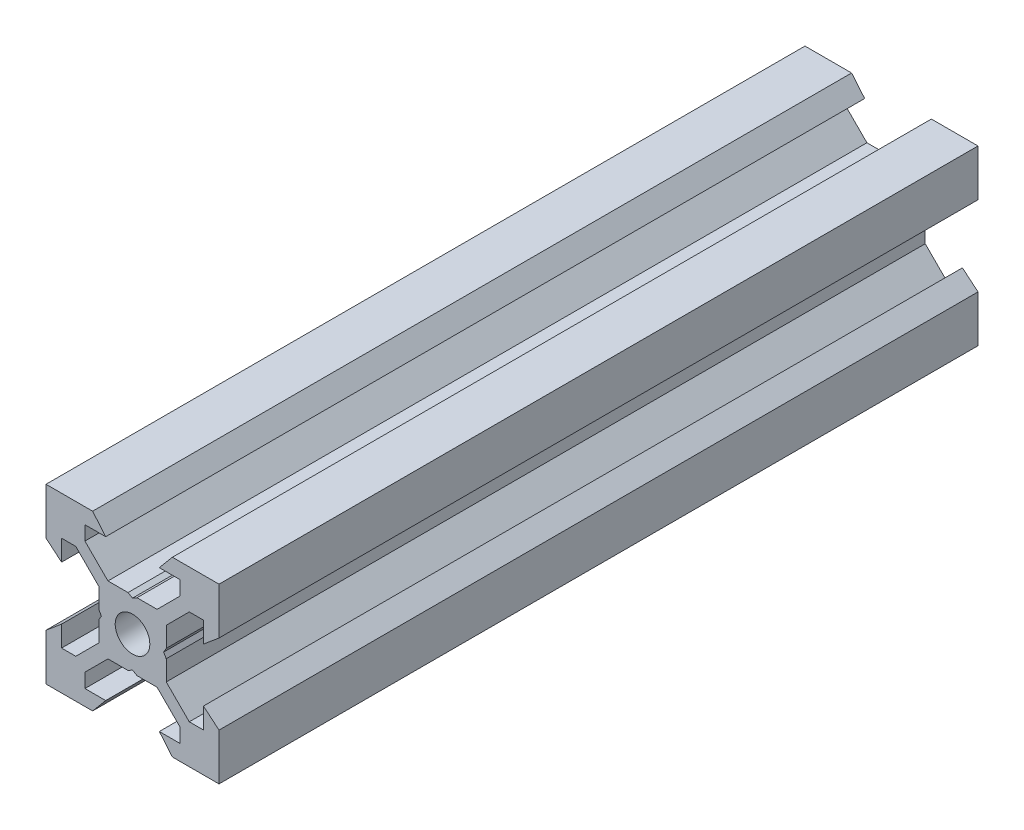
SolidWorks part; units mm, degrees
ref_plane "Front Plane" through (0, 0, 0) normal (0, 0, 1) x (1, 0, 0)
ref_plane "Top Plane" through (0, 0, 0) normal (0, 1, 0) x (1, 0, 0)
ref_plane "Right Plane" through (0, 0, 0) normal (1, 0, 0) x (0, 0, -1)
sketch "Sketch1" plane through (0, 0, 0) normal (0, 0, 1) x (1, 0, 0)
  line L0 (10, 10) -> (4.6104, 10) construction
  line L1 (10, 10) -> (10, 4.6104) construction
  line L2 (10, -10) -> (10, -4.6104) construction
  line L3 (10, -10) -> (4.6104, -10) construction
  line L4 (10, 10) -> (10, 4.6104)
  line L5 (6.5607, 5.5) -> (8.2, 5.5)
  line L6 (5.5, 8.2) -> (5.5, 6.5607)
  line L7 (10, 10) -> (4.6104, 10)
  line L8 (10, 10) -> (10, 4.6104)
  line L9 (6.5607, 5.5) -> (3.9, 2.8393)
  line L10 (5.5, 6.5607) -> (2.8393, 3.9)
  line L11 (10, 4.6104) -> (8.2, 3.1)
  line L12 (4.6104, 10) -> (3.1, 8.2)
  line L13 (8.2, 3.1) -> (8.2, 5.5)
  line L14 (3.1, 8.2) -> (5.5, 8.2)
  line L15 (-6.5607, 5.5) -> (-8.2, 5.5)
  line L16 (6.5607, -5.5) -> (8.2, -5.5)
  line L17 (3.1, -8.2) -> (5.5, -8.2)
  line L18 (8.2, -3.1) -> (8.2, -5.5)
  line L19 (4.6104, -10) -> (3.1, -8.2)
  line L20 (10, -4.6104) -> (8.2, -3.1)
  line L21 (0.5196, -3.9) -> (0, -3.6)
  line L22 (0.5196, 3.9) -> (0, 3.6)
  line L23 (3.6, 0) -> (3.9, -0.5196)
  line L24 (3.9, 0.5196) -> (3.6, 0)
  line L25 (3.9, 0.5196) -> (3.9, 2.8393)
  line L26 (2.8393, 3.9) -> (0.5196, 3.9)
  line L27 (3.9, -2.8393) -> (3.9, -0.5196)
  line L28 (2.8393, -3.9) -> (0.5196, -3.9)
  line L29 (5.5, -6.5607) -> (2.8393, -3.9)
  line L30 (6.5607, -5.5) -> (3.9, -2.8393)
  line L31 (10, -10) -> (10, -4.6104)
  line L32 (10, -10) -> (4.6104, -10)
  line L33 (5.5, -8.2) -> (5.5, -6.5607)
  line L34 (-6.5607, -5.5) -> (-8.2, -5.5)
  line L35 (10, -10) -> (10, -4.6104)
  line L36 (0, 0) -> (0, 8.2) construction
  line L37 (-10, -10) -> (-4.6104, -10) construction
  line L38 (-10, -10) -> (-10, -4.6104) construction
  line L39 (-10, 10) -> (-10, 4.6104) construction
  line L40 (-10, 10) -> (-4.6104, 10) construction
  line L41 (-10, -10) -> (-10, -4.6104)
  line L43 (-5.5, -8.2) -> (-5.5, -6.5607)
  line L44 (-10, -10) -> (-4.6104, -10)
  line L45 (-10, -10) -> (-10, -4.6104)
  line L46 (-6.5607, -5.5) -> (-3.9, -2.8393)
  line L47 (-5.5, -6.5607) -> (-2.8393, -3.9)
  line L48 (-2.8393, -3.9) -> (-0.5196, -3.9)
  line L49 (-3.9, -2.8393) -> (-3.9, -0.5196)
  line L50 (-2.8393, 3.9) -> (-0.5196, 3.9)
  line L51 (-3.9, 0.5196) -> (-3.9, 2.8393)
  line L52 (-3.9, 0.5196) -> (-3.6, 0)
  line L53 (-3.6, 0) -> (-3.9, -0.5196)
  line L54 (-0.5196, 3.9) -> (0, 3.6)
  line L55 (-0.5196, -3.9) -> (0, -3.6)
  line L56 (-10, -4.6104) -> (-8.2, -3.1)
  line L57 (-4.6104, -10) -> (-3.1, -8.2)
  line L58 (-8.2, -3.1) -> (-8.2, -5.5)
  line L59 (-3.1, -8.2) -> (-5.5, -8.2)
  line L60 (-10, -10) -> (10, -10) construction
  line L61 (-10, -10) -> (-10, 10) construction
  line L62 (-3.1, 8.2) -> (-5.5, 8.2)
  line L63 (-8.2, 3.1) -> (-8.2, 5.5)
  line L64 (-4.6104, 10) -> (-3.1, 8.2)
  line L65 (-10, 4.6104) -> (-8.2, 3.1)
  line L66 (-5.5, 6.5607) -> (-2.8393, 3.9)
  line L67 (-6.5607, 5.5) -> (-3.9, 2.8393)
  line L68 (-10, 10) -> (-10, 4.6104)
  line L69 (-10, 10) -> (-4.6104, 10)
  line L70 (-5.5, 8.2) -> (-5.5, 6.5607)
  line L71 (-10, 10) -> (10, 10) construction
  line L72 (-10, 10) -> (-10, 4.6104)
  line L73 (10, -10) -> (10, 10) construction
  line L74 (-10, -10) -> (10, 10) construction
  line L75 (-10, 10) -> (10, -10) construction
  circle A0 centre (0, 0) radius 2
  dimension "D7" = 4
  dimension "D1" = 20
  dimension "D2" = 5.3896
  dimension "D3" = 4.5
  dimension "D4" = 50
  dimension "D5" = 1.8
  dimension "D6" = 1.5104
  dimension "D8" = 5.5
  dimension "D9" = 120
  dimension "D10" = 0.3
  dimension "D11" = 2.3197
  dimension "D12" = 7.8
  dimension "D13" = 7.8
  dimension "D14" = 1.5
  dimension "D15" = 2.6607
extrude "Boss-Extrude1" add sketch "Sketch1" along normal mid plane 87.73 contours L70 L62 L64 L69 L68 L65 L63 L15 L67 L51 L52 L53 L49 L46 L34 L58 L56 L41 L44 L57 L59 L43 L47 L48 L55 L21 L28 L29 L33 L17 L19 L32 L31 L20 L18 L16 L30 L27 L23 L24 L25 L9 L5 L13 L11 L4 L7 L12 L14 L6 L10 region at (9.7172, 7.3052, 0)
